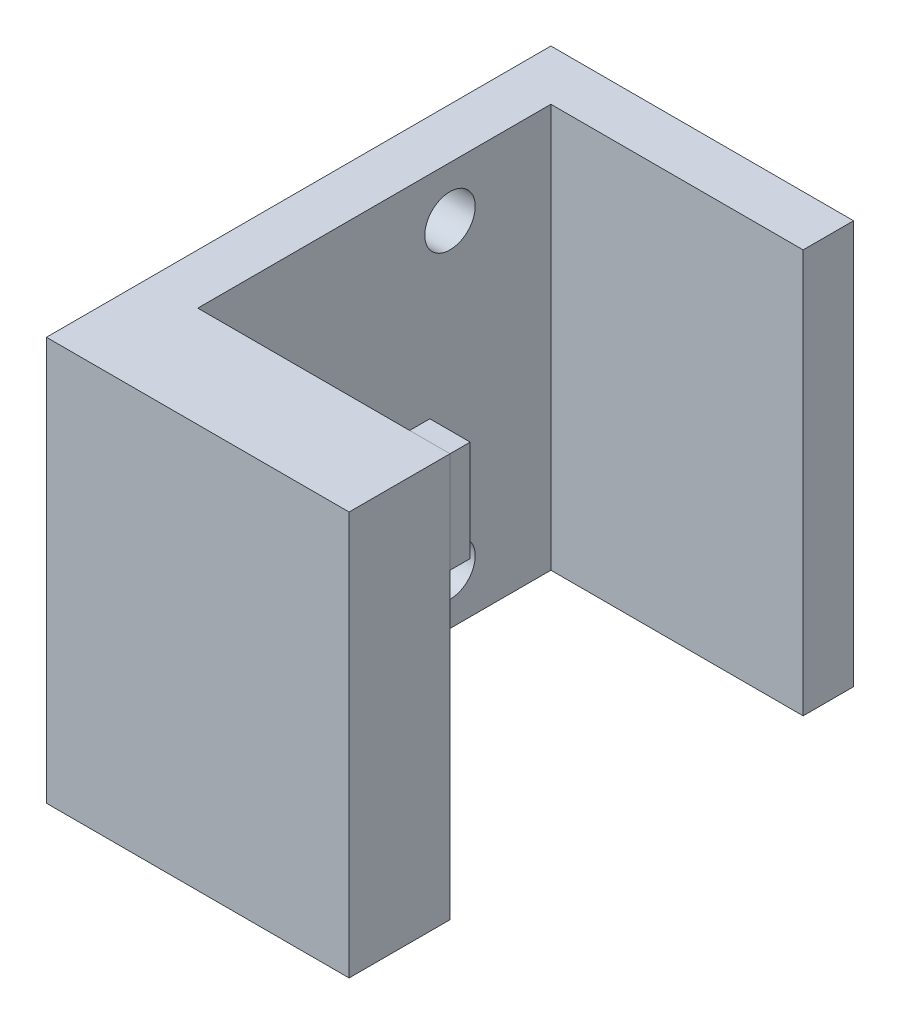
SolidWorks part; units mm, degrees
ref_plane "Front Plane" through (0, 0, 0) normal (0, 0, 1) x (1, 0, 0)
ref_plane "Top Plane" through (0, 0, 0) normal (0, 1, 0) x (1, 0, 0)
ref_plane "Right Plane" through (0, 0, 0) normal (1, 0, 0) x (0, 0, -1)
sketch "Sketch1" plane through (0, 0, 0) normal (0, 1, 0) x (1, 0, 0)
  line L0 (0, 225) -> (0, 250)
  line L1 (0, 0) -> (-150, 0)
  line L2 (0, 0) -> (0, 50)
  line L3 (0, 250) -> (-150, 250)
  line L4 (-150, 0) -> (-150, 250)
  line L5 (0, 50) -> (-125, 50)
  line L7 (0, 225) -> (-125, 225)
  line L8 (-125, 50) -> (-125, 225)
  dimension "D1" = 25
  dimension "D2" = 50
  dimension "D3" = 25
  dimension "D4" = 250
  dimension "D5" = 150
extrude "Boss-Extrude1" add sketch "Sketch1" along normal blind 200
sketch "Sketch2" plane through (-150, 0, 0) normal (-1, 0, 0) x (0, 0, 1)
  line L0 (-175, 175) -> (-175, 25) construction
  line L1 (-250, 200) -> (-250, 0) construction
  point P4 (-250, 100)
  point P5 (-175, 100)
  dimension "D1" = 75
  dimension "D2" = 150
hole_wizard "Hole1" positions "3DSketch1" profile "Sketch3" legacy end condition through all
sketch3d "3DSketch1"
  point P0 (-150, 175, -175)
  point P3 (-150, 25, -175)
  point P7 (-150, 25, -175)
sketch "Sketch3" plane through (-150, 175, -175) normal (0, 1, 0) x (0, 0, 1)
  line L0 (0, 0) -> (0, 150)
  line L1 (0, 150) -> (12.5, 150)
  line L2 (12.5, 150) -> (12.5, 0)
  line L3 (12.5, 0) -> (0, 0)
  line L4 (0, 110) -> (0, -10) construction
  dimension "Diameter" = 25
  dimension "Depth" = 150
sketch "Sketch4" plane through (0, 0, -50) normal (0, 0, -1) x (-1, 0, 0)
  line L1 (0, 200) -> (20, 200)
  line L2 (0, 200) -> (0, 150)
  line L3 (0, 150) -> (20, 150)
  line L4 (20, 200) -> (20, 150)
  dimension "D1" = 20
  dimension "D2" = 50
extrude "Boss-Extrude2" add sketch "Sketch4" along normal blind 10 separate body
